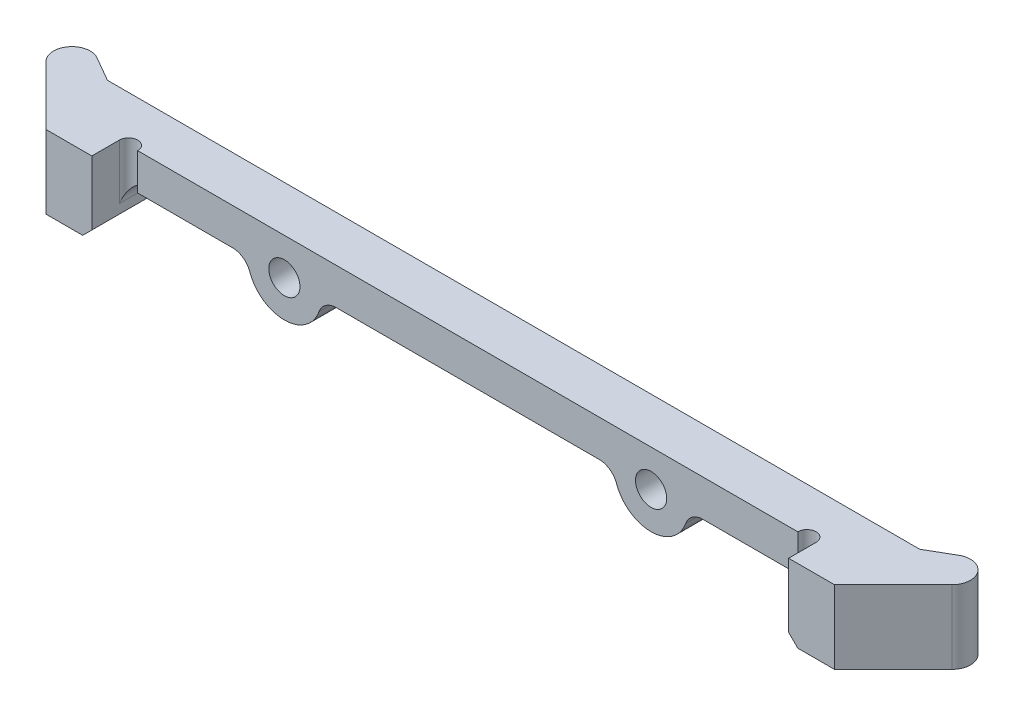
SolidWorks part; units mm, degrees
material "A2017"
ref_plane "正面" through (0, 0, 0) normal (0, 0, 1) x (1, 0, 0)
ref_plane "平面" through (0, 0, 0) normal (0, 1, 0) x (1, 0, 0)
ref_plane "右側面" through (0, 0, 0) normal (1, 0, 0) x (0, 0, -1)
sketch "ｽｹｯﾁ1" plane through (0, 0, 0) normal (0, 1, 0) x (1, 0, 0)
  line L0 (0, 0) -> (0, 22.3684) construction
  line L1 (-38, 0) -> (38, 0)
  line L2 (38, 0) -> (38, -3)
  line L3 (38, -3) -> (43, -3)
  line L4 (-38, -3) -> (-43, -3)
  line L5 (-38, 0) -> (-38, -3)
  line L6 (43, -3) -> (49.4142, 3.4142)
  line L7 (-43, -3) -> (-49.4142, 3.4142)
  line L8 (-44.2972, 5) -> (44.2972, 5)
  line L9 (47, 6.5605) -> (44.2972, 5)
  line L10 (50, 8.3293) -> (50, -3) construction
  line L11 (-50, 8.3293) -> (-50, -3) construction
  line L12 (-47, 6.5605) -> (-44.2972, 5)
  line L13 (-43, -3) -> (-49.4142, 3.4142)
  arc A0 (49.4142, 3.4142) -> (47, 6.5605) centre (48, 4.8284) ccw
  arc A1 (-49.4142, 3.4142) -> (-47, 6.5605) centre (-48, 4.8284) cw
  point P14 (0, 5)
  dimension "D8" = 2
  dimension "D1" = 5
  dimension "D2" = 3
  dimension "D3" = 76
  dimension "D4" = 45
  dimension "D5" = 30
  dimension "D6" = 5
  dimension "D7" = 100
extrude "ﾎﾞｽ - 押し出し1" add sketch "ｽｹｯﾁ1" along normal mid plane 8 contours A1 L7 L4 L5 L1 L2 L3 L6 A0 L9 L8 L12 region at (0, 0, -2.3316)
sketch "ｽｹｯﾁ2" plane through (0, 4, 0) normal (0, 1, 0) x (1, 0, 0)
  line L0 (-38, 0) -> (38, 0) construction
  circle A0 centre (-37, 0) radius 1
  circle A1 centre (37, 0) radius 1
  dimension "D1" = 2
extrude "ｶｯﾄ - 押し出し1" cut sketch "ｽｹｯﾁ2" against normal up to surface (8 mm away) up to face at (0, -4, -1.6722)
hole_wizard "M3 すきま穴1" positions "ｽｹｯﾁ3" profile "ｽｹｯﾁ4" hole size "M3" standard "JIS" end condition through all
sketch "ｽｹｯﾁ3" plane through (0, 0, 0) normal (0, 0, 1) x (1, 0, 0)
  point P0 (20, 0)
  point P3 (-20, 0)
sketch "ｽｹｯﾁ4" plane through (20, 0, 0) normal (1, 0, 0) x (0, -1, 0)
  line L0 (0, 0) -> (0, 6.8284)
  line L1 (0, 6.8284) -> (1.7, 6.8284)
  line L2 (1.7, 6.8284) -> (1.7, 0)
  line L5 (1.7, 0) -> (0, 0)
  line L11 (0, -6.35) -> (0, 107.95) construction
  dimension "通し穴の直径" = 3.4
  dimension "通し穴の深さ" = 6.8284
sketch "ｽｹｯﾁ5" plane through (0, 0, 0) normal (0, 0, 1) x (1, 0, 0)
  line L0 (-36, 4) -> (36, 4) construction
  line L2 (-38, -4) -> (38, -4)
  line L3 (-38, -4) -> (-38, 0)
  line L4 (-38, 0) -> (38, 0)
  line L5 (38, -4) -> (38, 0)
  line L6 (38, 4) -> (38, -4) construction
  circle A0 centre (-20, 0) radius 4
  circle A1 centre (20, 0) radius 4
  point P13 (38, 0)
  line M3 (-36, -4) -> (36, -4)
  line M4 (36, -4) -> (36, 4)
  line M6 (-36, 4) -> (-36, -4)
extrude "ｶｯﾄ - 押し出し2" cut sketch "ｽｹｯﾁ5" against normal through all contours A0 L4 M6 M3 | A1 L4 A0 L2 | A1 L4 M3 M4 | L2 L5 L4 M4 | L4 L3 L2 M6 region at (-37, -2, 0) region at (-29.5398, -2.0739, 0) region at (0, -2.0563, 0) region at (29.5398, -2.0739, 0) region at (37, -2, 0)
fillet "ﾌｨﾚｯﾄ1" radius 2 6 edges at (38, 0, -2.5) (24, 0, -2.5) (16, 0, -2.5) (-16, 0, -2.5) (-24, 0, -2.5) (-38, 0, -2.5)
chamfer "面取り1" distance 1 angle 45 2 edges at (-38, -4, -1) (38, -4, -1)
